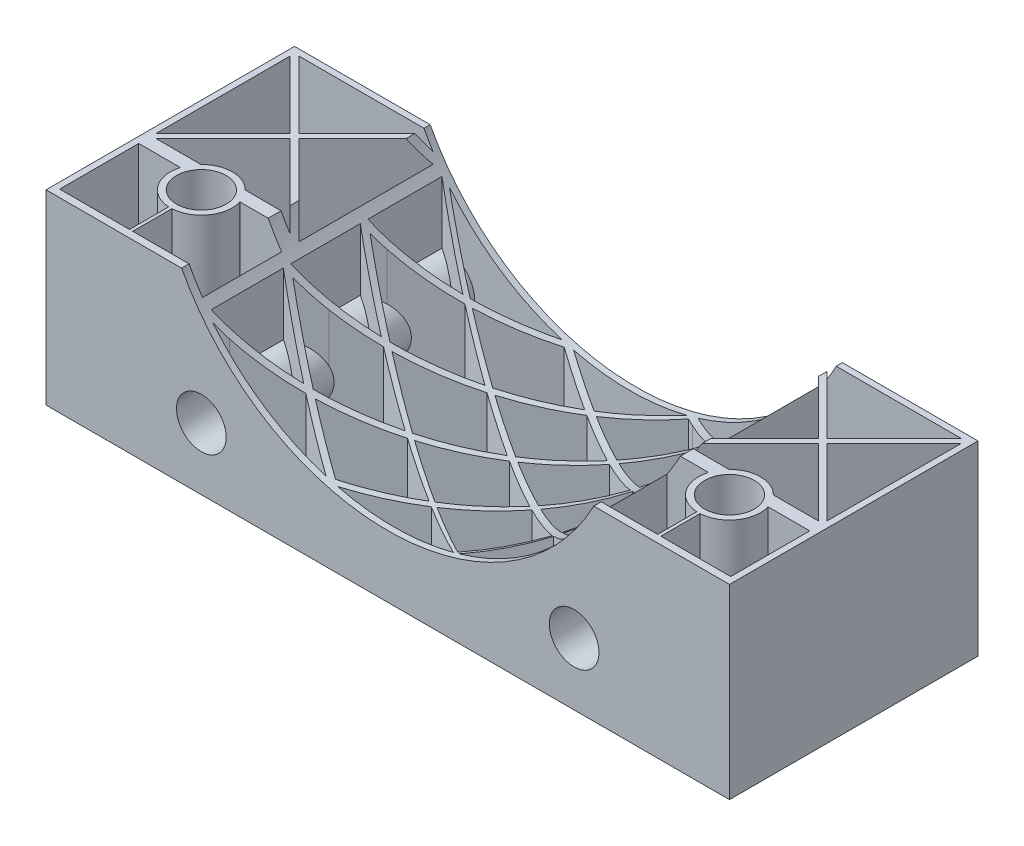
SolidWorks part; units mm, degrees
ref_plane "Front Plane" through (0, 0, 0) normal (0, 0, 1) x (1, 0, 0)
ref_plane "Top Plane" through (0, 0, 0) normal (0, 1, 0) x (1, 0, 0)
ref_plane "Right Plane" through (0, 0, 0) normal (1, 0, 0) x (0, 0, -1)
other "Center of Mass"
ref_plane "Plane1" through (55, 0, 0) normal (1, 0, 0) x (0, 0, -1)
sketch "Sketch1" plane through (0, 0, 0) normal (0, 1, 0) x (1, 0, 0)
  line L1 (0, 0) -> (110, 0)
  line L2 (0, 0) -> (0, 40)
  line L3 (0, 40) -> (110, 40)
  line L4 (110, 0) -> (110, 40)
  dimension "D1" = 110
  dimension "D2" = 40
extrude "Boss-Extrude1" add sketch "Sketch1" along normal blind 30
sketch "Sketch2" plane through (0, 0, 0) normal (0, 0, 1) x (1, 0, 0)
  line L0 (55, 0) -> (55, 10) construction
  line L1 (0, 0) -> (110, 0) construction
  line L2 (55, 10) -> (55, 47.5) construction
  circle A0 centre (55, 47.5) radius 37.5
  point P5 (55, 0)
  dimension "D2" = 75
  dimension "D1" = 10
extrude "Cut-Extrude1" cut sketch "Sketch2" against normal blind 40
sketch "Sketch3" plane through (0, 0, 0) normal (0, -1, 0) x (1, 0, 0)
  line L0 (110, -20) -> (85, -20) construction
  line L2 (110, 0) -> (110, -40) construction
  line L3 (0, -40) -> (0, 0) construction
  line L4 (0, -20) -> (25, -20) construction
  line L5 (0, -12.5) -> (12.5, -12.5) construction
  line L6 (12.5, -12.5) -> (12.5, 0) construction
  line L7 (0, 0) -> (110, 0) construction
  circle A0 centre (12.5, -12.5) radius 4
  dimension "D5" = 8
  dimension "D1" = 25
  dimension "D2" = 25
  dimension "D3" = 12.5
  dimension "D4" = 12.5
extrude "Cut-Extrude3" cut sketch "Sketch3" against normal blind 30
mirror "Mirror1" about plane through (55, 0, 0) normal (1, 0, 0) of "Cut-Extrude3"
sketch "Sketch7" plane through (0, 0, 0) normal (0, 0, 1) x (1, 0, 0)
  line L2 (55, -16.5) -> (55, 16.5) construction
  circle A2 centre (25, 10) radius 4
  circle A4 centre (85, 10) radius 4
  dimension "D1" = 60
extrude "Cut-Extrude6" cut sketch "Sketch7" against normal blind 40
sketch "Sketch9" plane through (0, 0, 0) normal (0, -1, 0) x (1, 0, 0)
  line L0 (12.5, -12.5) -> (12.5, 0) construction
  line L1 (0, 0) -> (110, 0) construction
  line L2 (12.5, 0) -> (12.5, -40) construction
  line L3 (110, -40) -> (0, -40) construction
  line L4 (1.7071, -39) -> (12.5, -28.2071)
  line L5 (25, 0) -> (25, -40) construction
  line L6 (1.7071, -39) -> (21.7913, -39)
  line L7 (0, -40) -> (0, 0) construction
  line L8 (25, -40) -> (0, -15) construction
  line L9 (0, -15) -> (25, -15) construction
  line L10 (25, -15) -> (0, -40) construction
  line L11 (12.5, -28.2071) -> (23.2929, -39)
  line L12 (23.2929, -39) -> (21.7913, -39)
  line L13 (1, -16.7071) -> (11.7929, -27.5)
  line L14 (1, -38.2929) -> (1, -36.7913)
  line L15 (11.7929, -27.5) -> (1, -38.2929)
  line L16 (1, -16.7071) -> (1, -36.7913)
  line L17 (23.2929, -16) -> (12.5, -26.7929)
  line L19 (12.5, -26.7929) -> (1.7071, -16)
  line L21 (24, -38.2929) -> (13.2071, -27.5)
  line L22 (24, -16.7071) -> (24, -18.2087)
  line L23 (13.2071, -27.5) -> (24, -16.7071)
  line L24 (24, -38.2929) -> (24, -18.2087)
  line L26 (1.7071, -16) -> (8.9293, -16)
  line L27 (23.2929, -16) -> (16.3426, -16) [skipped]
  line L28 (1.7071, -16) -> (3.2087, -16) [skipped]
  line L29 (16.0707, -16) -> (23.2929, -16)
  line L31 (12.25, -1.1996) -> (1, -1.1996)
  line L32 (1, -1.1996) -> (1, -13.9249)
  line L33 (12.25, -1.1996) -> (12.25, -7.5063)
  line L34 (1, -13.9249) -> (7.7073, -13.9249)
  line L35 (7.7073, -13.9249) -> (7.6892, -13.8624)
  line L36 (17.2927, -13.9249) -> (17.3108, -13.8624)
  line L37 (12.75, -1.1996) -> (12.75, -7.5063)
  line L38 (24, -13.9249) -> (17.2927, -13.9249)
  line L39 (24, -1.1996) -> (24, -13.9249)
  line L40 (12.75, -1.1996) -> (24, -1.1996)
  line L41 (55, -16.5) -> (55, 16.5) construction
  line L42 (85, -15) -> (110, -40) construction
  line L43 (110, -15) -> (85, -15) construction
  line L44 (85, -40) -> (110, -15) construction
  line L45 (85, 0) -> (85, -40) construction
  line L46 (97.5, 0) -> (97.5, -40) construction
  line L47 (97.5, -12.5) -> (97.5, 0) construction
  line L48 (97.25, -1.1996) -> (86, -1.1996)
  line L49 (86, -1.1996) -> (86, -13.9249)
  line L50 (86, -13.9249) -> (92.7073, -13.9249)
  line L51 (97.25, -1.1996) -> (97.25, -7.5063)
  line L52 (92.7073, -13.9249) -> (92.6892, -13.8624)
  line L53 (102.2927, -13.9249) -> (102.3108, -13.8624)
  line L54 (109, -13.9249) -> (102.2927, -13.9249)
  line L55 (97.75, -1.1996) -> (97.75, -7.5063)
  line L56 (109, -1.1996) -> (109, -13.9249)
  line L57 (97.75, -1.1996) -> (109, -1.1996)
  line L58 (93.9293, -16) -> (86.7071, -16)
  line L59 (108.2929, -16) -> (101.0707, -16)
  line L60 (86, -38.2929) -> (86, -18.2087)
  line L61 (96.7929, -27.5) -> (86, -16.7071)
  line L62 (86, -16.7071) -> (86, -18.2087)
  line L63 (86, -38.2929) -> (96.7929, -27.5)
  line L64 (97.5, -26.7929) -> (108.2929, -16)
  line L65 (86.7071, -16) -> (97.5, -26.7929)
  line L66 (109, -16.7071) -> (109, -36.7913)
  line L67 (98.2071, -27.5) -> (109, -38.2929)
  line L68 (109, -38.2929) -> (109, -36.7913)
  line L69 (109, -16.7071) -> (98.2071, -27.5)
  line L70 (86.7071, -39) -> (88.2087, -39)
  line L71 (97.5, -28.2071) -> (86.7071, -39)
  line L72 (108.2929, -39) -> (88.2087, -39)
  line L73 (108.2929, -39) -> (97.5, -28.2071)
  circle A1 centre (12.5, -12.5) radius 4 construction
  arc A3 (8.9293, -16) -> (16.0707, -16) centre (12.5, -12.5) ccw
  arc A5 (12.25, -7.5063) -> (7.6892, -13.8624) centre (12.5, -12.5) ccw
  arc A6 (12.75, -7.5063) -> (17.3108, -13.8624) centre (12.5, -12.5) cw
  arc A7 (97.25, -7.5063) -> (92.6892, -13.8624) centre (97.5, -12.5) ccw
  arc A8 (97.75, -7.5063) -> (102.3108, -13.8624) centre (97.5, -12.5) cw
  arc A9 (101.0707, -16) -> (93.9293, -16) centre (97.5, -12.5) cw
  point P18 (12.5, -27.5)
  point P36 (12.5, -27.5)
  point P39 (12.5, -16.5)
  point P40 (10.5635, -16)
  point P41 (14.4365, -16)
  point P50 (8.9293, -16)
  point P52 (12.25, -7.5063)
  point P53 (7.7073, -13.9249)
  point P98 (102.2927, -13.9249)
  point P99 (97.75, -7.5063)
  point P100 (101.0707, -16)
  point P101 (95.5635, -16)
  point P102 (99.4365, -16)
  point P103 (97.5, -16.5)
  point P104 (97.5, -27.5)
  dimension "D5" = 0.5
  dimension "D1" = 12.5
  dimension "D2" = 1
  dimension "D3" = 0.5
  dimension "D4" = 4
extrude "Cut-Extrude7" cut sketch "Sketch9" against normal blind 30
sketch "Sketch11" plane through (0, 0, 0) normal (0, -1, 0) x (1, 0, 0)
  line L0 (25, -1) -> (25, -39) construction
  line L1 (25, -39) -> (85, -39) construction
  line L2 (85, -39) -> (85, -1) construction
  line L3 (85, -1) -> (25, -1) construction
  line L4 (0, 0) -> (110, 0) construction
  line L5 (24, -13.9249) -> (24, -1.1996) construction
  line L6 (110, -40) -> (0, -40) construction
  line L7 (86, -16.7071) -> (86, -38.2929) construction
  line L8 (55, -1) -> (55, -39) construction
  line L9 (25, -20) -> (54, -20) construction
  line L10 (85, -1) -> (65, -1)
  line L11 (65, -1) -> (45, -1)
  line L12 (45, -1) -> (25, -1)
  line L13 (25, -1) -> (25, -13.6)
  line L14 (25, -13.6) -> (25, -26.2)
  line L15 (25, -26.2) -> (25, -39)
  line L16 (85, -39) -> (65, -39)
  line L17 (45, -39) -> (25, -39)
  line L18 (85, -39) -> (25, -39) construction
  line L19 (65, -39) -> (45, -39)
  line L20 (25, -13.8) -> (25, -1)
  line L21 (85, -26.2) -> (85, -39)
  line L22 (85, -1) -> (85, -13.6)
  line L23 (85, -13.6) -> (85, -26.2)
  line L24 (25, -13.8) -> (45, -1) construction
  line L25 (25, -26.2) -> (65, -1) construction
  line L26 (25, -39) -> (85, -1) construction
  line L27 (45, -39) -> (85, -13.6) construction
  line L28 (65, -39) -> (85, -26.2) construction
  line L29 (85, -13.6) -> (65, -1) construction
  line L30 (85, -26.2) -> (45, -1) construction
  line L31 (85, -39) -> (25, -1) construction
  line L32 (65, -39) -> (25, -13.8) construction
  line L33 (25.86, -2.1365) -> (81.8164, -37.5756)
  line L34 (25.9456, -2.1907) -> (25, -1.5918)
  line L35 (81.8164, -37.5756) -> (84.0655, -39)
  line L36 (27.2382, -1.8257) -> (83.9174, -37.7225)
  line L37 (27.5296, -2.0103) -> (25.86, -1)
  line L38 (83.9174, -37.7225) -> (85, -38.4082)
  line L39 (28.4232, -12.2028) -> (38.2658, -5.9035)
  line L40 (38.2658, -5.9035) -> (45.9276, -1)
  line L41 (37.2659, -5.3562) -> (44.0724, -1)
  line L42 (37.2659, -5.3562) -> (27.9267, -11.3333)
  line L43 (27.9267, -11.3333) -> (25, -13.2064)
  line L44 (47.7229, -3.3064) -> (79.6333, -23.4099)
  line L45 (79.6333, -23.4099) -> (85, -26.791)
  line L46 (47.7229, -3.3064) -> (44.0724, -1)
  line L47 (45.9276, -1) -> (81.2018, -23.2162)
  line L48 (81.2018, -23.2162) -> (85, -25.6083)
  line L49 (63.0254, -2.5395) -> (28.312, -24.7044)
  line L50 (28.312, -24.7044) -> (25, -26.8191)
  line L51 (28.3301, -23.5111) -> (61.7814, -2.7322)
  line L52 (61.7814, -2.7322) -> (64.5701, -1)
  line L53 (63.0254, -2.5395) -> (65.4364, -1)
  line L54 (65.4364, -1) -> (69.4058, -3.4802)
  line L55 (69.4058, -3.4802) -> (85, -13.2239)
  line L56 (64.5701, -1) -> (67.6965, -2.9943)
  line L57 (67.6965, -2.9943) -> (85, -14.0318)
  line L58 (85, -14.0318) -> (81.3497, -16.5102)
  line L59 (67.4512, -38.0249) -> (82.2284, -28.5675)
  line L60 (82.2284, -28.5675) -> (85, -26.791)
  line L61 (67.4512, -38.0249) -> (65.9299, -39)
  line L62 (65.9299, -39) -> (29.5093, -16.0499)
  line L63 (29.5093, -16.0499) -> (25, -13.2064)
  line L64 (28.0981, -16.3428) -> (62.6323, -38.0993)
  line L65 (62.6323, -38.0993) -> (64.062, -39)
  line L66 (28.0981, -16.3428) -> (25, -14.391)
  line L67 (28.3301, -23.5111) -> (25, -25.5796)
  line L68 (29.5859, -36.6874) -> (82.8637, -2.9448)
  line L69 (82.8637, -2.9448) -> (85, -1.5918)
  line L70 (78.5744, -4.4777) -> (29.2621, -36.0047)
  line L71 (29.2621, -36.0047) -> (25, -38.7297)
  line L72 (29.5859, -36.6874) -> (25.9345, -39)
  line L73 (47.1403, -38.2332) -> (81.3497, -16.5102)
  line L74 (80.4967, -15.8673) -> (46.2437, -37.6179)
  line L75 (46.2437, -37.6179) -> (44.0673, -39)
  line L76 (80.4967, -15.8673) -> (85, -13.0077)
  line L77 (78.5744, -4.4777) -> (84.014, -1)
  line L78 (47.1403, -38.2332) -> (45.9276, -39)
  line L79 (66.8535, -37.2201) -> (80.6496, -28.3906)
  line L80 (80.6496, -28.3906) -> (85, -25.6083)
  line L81 (66.8535, -37.2201) -> (64.062, -39)
  line L82 (28.4232, -12.2028) -> (25, -14.391)
  line L83 (25, -26.2) -> (45, -39) construction
  line L84 (26.8548, -27.9807) -> (42.5394, -38.0189)
  line L85 (42.5394, -38.0189) -> (44.0673, -39)
  line L86 (26.8548, -27.9807) -> (25, -26.8191)
  line L87 (27.6269, -27.2876) -> (43.5979, -37.5091)
  line L88 (43.5979, -37.5091) -> (45.9276, -39)
  line L89 (27.6269, -27.2876) -> (25, -25.5796)
  point P18 (35, 7.2209)
  point P35 (82.8637, -2.9448)
  point P37 (29.5859, -36.6874)
  point P38 (29.2621, -36.0047)
  point P39 (28.312, -24.7044)
  point P40 (28.3301, -23.5111)
  point P41 (28.0981, -16.3428)
  point P42 (29.5093, -16.0499)
  point P43 (28.4232, -12.2028)
  point P44 (27.9267, -11.3333)
  point P45 (37.2659, -5.3562)
  point P46 (38.2658, -5.9035)
  point P47 (49.0942, -2.9884)
  point P48 (47.7229, -3.3064)
  point P49 (81.2018, -23.2162)
  point P50 (79.6333, -23.4099)
  point P51 (80.6496, -28.3906)
  point P52 (82.2284, -28.5675)
  point P53 (80.4967, -15.8673)
  point P54 (81.3497, -16.5102)
  point P55 (81.5522, -11.1324)
  point P56 (81.3412, -11.8859)
  point P57 (69.4058, -3.4802)
  point P58 (67.6965, -2.9943)
  point P59 (61.7814, -2.7322)
  point P60 (63.0254, -2.5395)
  point P84 (47.1403, -38.2332)
  point P86 (46.2437, -37.6179)
  point P87 (62.6323, -38.0993)
  point P88 (67.4512, -38.0249)
  point P100 (78.5744, -4.4777)
  point P110 (66.8535, -37.2201)
  point P116 (27.6269, -27.2876)
  point P117 (26.8548, -27.9807)
  point P118 (42.5394, -38.0189)
  point P119 (43.5979, -37.5091)
  dimension "D1" = 1
  dimension "D2" = 1
  dimension "D3" = 1
  dimension "D4" = 1
  dimension "D5" = 1
  dimension "D6" = 0.5
  dimension "D7" = 0.5
  dimension "D8" = 0.5
  dimension "D9" = 0.5
  dimension "D10" = 0.5
  dimension "D11" = 0.5
  dimension "D12" = 0.5
  dimension "D13" = 0.5
  dimension "D14" = 0.5
  dimension "D15" = 0.5
  dimension "D16" = 0.5
  dimension "D17" = 0.5
  dimension "D18" = 0.5
  dimension "D19" = 0.5
  dimension "D20" = 0.5
  dimension "D21" = 0.5
  dimension "D22" = 0.5
  dimension "D23" = 0.5
  dimension "D24" = 0.5
  dimension "D25" = 0.5
  dimension "D26" = 0.5
  dimension "D27" = 0.5
  dimension "D28" = 0.5
  dimension "D29" = 0.5
  dimension "D30" = 0.5
  dimension "D31" = 0.5
  dimension "D32" = 0.5
  dimension "D33" = 0.5
  dimension "D34" = 0.5
  dimension "D35" = 0.5
  dimension "D36" = 0.5
  dimension "D37" = 0.5
  dimension "D38" = 0.5
  dimension "D39" = 0.5
  dimension "D40" = 0.5
  dimension "D41" = 0.5
  dimension "D42" = 0.5
extrude "Cut-Extrude9" cut sketch "Sketch11" against normal blind 30 contours L42 L41 L12 L37 L36 | L43 L42 L33 L34 L20 | L39 L82 L63 L62 L51 L33 | L36 L51 L44 L46 L40 L39 | L51 L52 L11 L47 | L67 L51 L64 L66 L14 | L89 L87 L70 L64 L49 L50 | L84 L86 L15 L71 L70 | L85 L84 L68 L72 L17 | L87 L88 L75 L74 L64 L68 | L70 L33 L49 L62 | L70 L44 L49 L36 | L70 L57 L56 L53 L49 L47 | L70 L77 L10 L54 L55 | L55 L76 L22 L69 L68 | L74 L76 L57 L68 L47 | L74 L44 L68 L36 | L74 L33 L68 L62 | L81 L79 L33 L73 L62 | L73 L78 L19 L65 L64 | L79 L80 L45 L44 L73 L36 | L73 L47 L48 L23 L58 | L60 L59 L36 L38 L21 | L59 L61 L16 L35 L33 region at (74.7607, 0, -2.9568) region at (81.9172, 0, -7.419) region at (65.0368, 0, -7.1857) region at (55.2273, 0, -2.9434) region at (75.1028, 0, -13.5666) region at (82.0015, 0, -19.8799) region at (45.0868, 0, -7.3656) region at (54.9723, 0, -13.6251) region at (65.0173, 0, -19.9708) region at (35.0131, 0, -2.9234) region at (74.9895, 0, -26.2724) region at (44.9596, 0, -20.0172) region at (81.9597, 0, -32.6107) region at (54.9667, 0, -26.3397) region at (35.0085, 0, -13.7155) region at (28.0405, 0, -7.389) region at (35.0517, 0, -26.3591) region at (64.9645, 0, -32.658) region at (44.9944, 0, -32.6738) region at (27.9809, 0, -19.9985) region at (74.9809, 0, -37.0754) region at (28.111, 0, -32.765) region at (54.9851, 0, -37.089) region at (35.0189, 0, -37.0753)
sketch "Sketch12" plane through (0, 0, 0) normal (0, 0, 1) x (1, 0, 0)
  line L0 (55, -16.5) -> (55, 16.5) construction
  circle A0 centre (25, 10) radius 5
  circle A1 centre (85, 10) radius 5
  point P0 (25, 10)
  dimension "D1" = 10
extrude "Boss-Extrude3" add sketch "Sketch12" against normal blind 40
sketch "Sketch15" plane through (0, 0, 0) normal (0, 0, 1) x (1, 0, 0)
  line L0 (55, -16.5) -> (55, 16.5) construction
  circle A0 centre (25, 10) radius 4
  circle A1 centre (85, 10) radius 4
  point P0 (25, 10)
  dimension "D1" = 8
extrude "Cut-Extrude10" cut sketch "Sketch15" against normal blind 40
